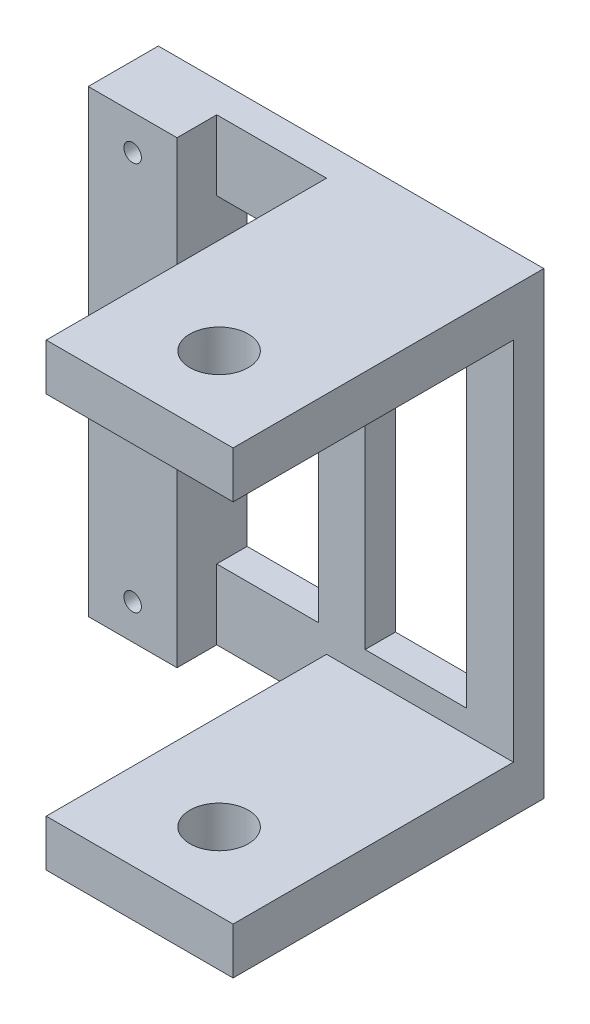
SolidWorks part; units mm, degrees
ref_plane "前视基准面" through (0, 0, 0) normal (0, 0, 1) x (1, 0, 0)
ref_plane "上视基准面" through (0, 0, 0) normal (0, 1, 0) x (1, 0, 0)
ref_plane "右视基准面" through (0, 0, 0) normal (1, 0, 0) x (0, 0, -1)
sketch "草图2" plane through (0, 0, 0) normal (0, 0, 1) x (1, 0, 0)
  line L3 (-9.15, -9.825) -> (7.35, -9.825)
  line L4 (7.35, 9.825) -> (7.35, -9.825)
  line L5 (0, 0) -> (2.4933, 0) construction
  line L6 (0, 0) -> (0, -3.9686) construction
  line L15 (-9.15, 9.825) -> (7.35, 9.825)
  line L16 (-5.35, 6.825) -> (-1, 6.825)
  line L17 (-5.35, 6.825) -> (-5.35, -6.825)
  line L18 (-5.35, -6.825) -> (-1, -6.825)
  line L20 (-9.15, 9.825) -> (-9.15, -9.825)
  line L21 (1, 6.825) -> (5.35, 6.825)
  line L23 (1, -6.825) -> (1, 6.825)
  line L25 (-1, -6.825) -> (-1, 6.825)
  line L26 (5.35, 6.825) -> (5.35, -6.825)
  line L28 (1, -6.825) -> (5.35, -6.825)
  point P0 (0, 0)
  dimension "D1" = 16.5
  dimension "D3" = 19.65
  dimension "D4" = 3.8
  dimension "D5" = 3
  dimension "D6" = 2
  dimension "D8" = 3
  dimension "D9" = 2
extrude "凸台-拉伸1" add sketch "草图2" along normal blind 1.3
sketch "草图3" plane through (0, 0, 1.3) normal (0, 0, 1) x (1, 0, 0)
  line L1 (-0.65, 9.825) -> (7.35, 9.825)
  line L2 (-0.65, 9.825) -> (-0.65, 7.825)
  line L3 (-0.65, 7.825) -> (7.35, 7.825)
  line L4 (7.35, 9.825) -> (7.35, 7.825)
  line L5 (7.35, -9.825) -> (7.35, 9.825) construction
  line L6 (-0.65, -7.825) -> (7.35, -7.825)
  line L8 (-0.65, -9.825) -> (7.35, -9.825)
  line L9 (7.35, -7.825) -> (7.35, -9.825)
  line L10 (-9.15, -9.825) -> (7.35, -9.825) construction
  line L11 (-0.65, -7.825) -> (-0.65, -9.825)
  line L12 (7.35, 9.825) -> (-9.15, 9.825) construction
  dimension "D1" = 2
  dimension "D2" = 2
  dimension "D3" = 8
  dimension "D4" = 8
extrude "凸台-拉伸2" add sketch "草图3" along normal blind 12
sketch "草图10" plane through (0, 0, 1.3) normal (0, 0, 1) x (1, 0, 0)
  line L0 (-9.15, 9.825) -> (-9.15, -9.825) construction
  line L1 (-9.15, 9.825) -> (-5.35, 9.825)
  line L2 (-9.15, 9.825) -> (-9.15, -9.825)
  line L3 (-9.15, -9.825) -> (-5.35, -9.825)
  line L4 (-5.35, 9.825) -> (-5.35, -9.825)
  line L5 (-0.65, 9.825) -> (-9.15, 9.825) construction
  line L6 (-9.15, -9.825) -> (-0.65, -9.825) construction
  line L7 (-5.35, 6.825) -> (-5.35, -6.825) construction
extrude "凸台-拉伸4" add sketch "草图10" along normal blind 1.7
sketch "草图9" plane through (0, 0, 1.3) normal (0, 0, 1) x (1, 0, 0)
  line L0 (-0.65, 9.825) -> (-5.35, 9.825) construction
  line L1 (-9.15, 9.825) -> (-9.15, -9.825) construction
  line L2 (-5.35, -9.825) -> (-0.65, -9.825) construction
  circle A0 centre (-7.25, 8.325) radius 0.375
  circle A1 centre (-7.25, -8.325) radius 0.375
  dimension "D1" = 0.75
  dimension "D2" = 0.75
  dimension "D3" = 1.5
  dimension "D4" = 1.9
  dimension "D5" = 1.5
  dimension "D6" = 1.9
extrude "切除-拉伸2" cut sketch "草图9" against normal up to next from surface starting at face at (-7.25, 0, 3)
sketch "草图11" plane through (0, -9.825, 0) normal (0, -1, 0) x (1, 0, 0)
  circle A0 centre (3.45, 10) radius 1.25
  dimension "D1" = 2.5
extrude "切除-拉伸3" cut sketch "草图11" against normal through all
